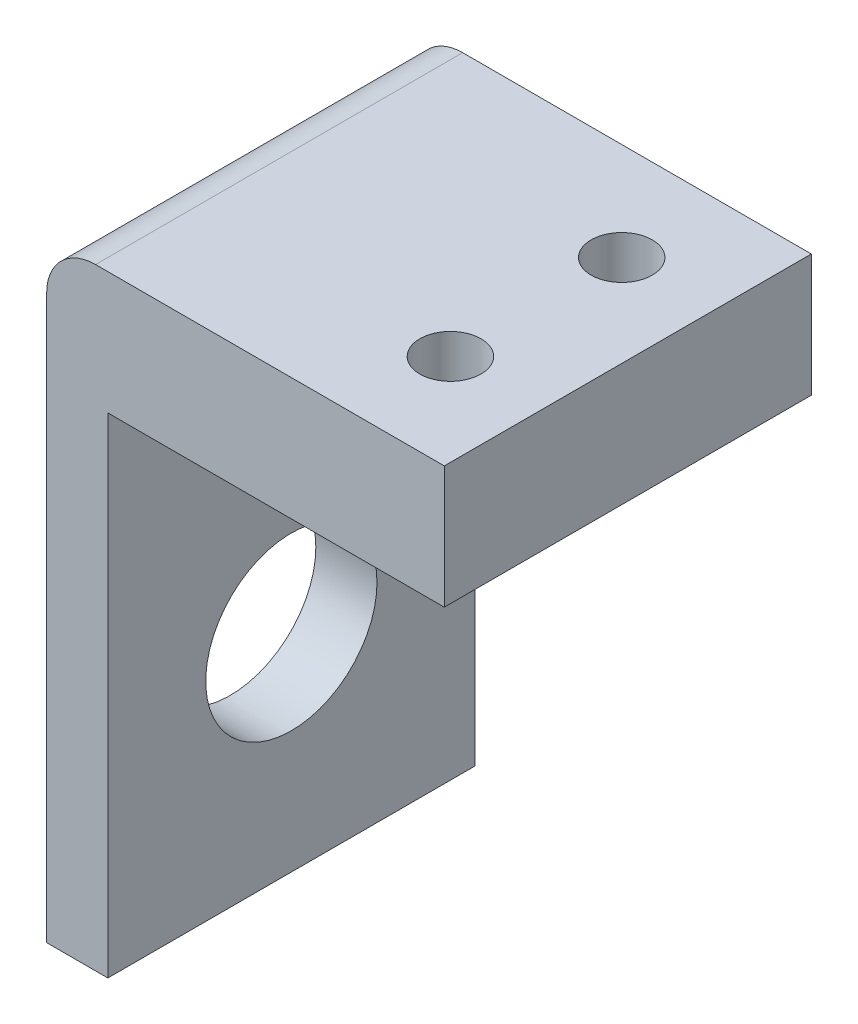
SolidWorks part; units mm, degrees
ref_plane "Front Plane" through (0, 0, 0) normal (0, 0, 1) x (1, 0, 0)
ref_plane "Top Plane" through (0, 0, 0) normal (0, 1, 0) x (1, 0, 0)
ref_plane "Right Plane" through (0, 0, 0) normal (1, 0, 0) x (0, 0, -1)
sketch "Sketch1" plane through (0, 0, 0) normal (1, 0, 0) x (0, 0, -1)
  line L0 (0, -7) -> (0, -17)
  line L1 (0, -17) -> (15, -17)
  line L2 (15, -17) -> (15, 33)
  line L3 (15, 33) -> (0, 33)
  line L4 (0, 33) -> (0, 23)
  line L5 (0, 23) -> (0, 7)
  line L6 (0, 33) -> (-15, 33)
  line L7 (-15, 33) -> (-15, -17)
  line L8 (-15, -17) -> (0, -17)
  line L9 (0, 23) -> (-15, 23)
  line L10 (0, 23) -> (15, 23)
  circle A0 centre (0, 0) radius 7
  dimension "D1" = 14
  dimension "D2" = 10
  dimension "D3" = 15
  dimension "D4" = 15
  dimension "D5" = 50
  dimension "D6" = 10
extrude "Boss-Extrude2" add sketch "Sketch1" along normal mid plane 5 contours A0 L5 L9 L7 L8 L0 | A0 L0 L1 L2 L10 L5 region at (0, 3.4415, -8.1665) region at (0, 3.4415, 8.1665)
extrude "Boss-Extrude3" add sketch "Sketch1<7>" along normal blind 30 and the other way blind 2.5 contours L9 L4 L6 L7 | L4 L10 L2 L3 region at (0, 28, 7.5) region at (0, 28, -7.5)
sketch "Sketch1<7>" plane through (0, 0, 0) normal (1, 0, 0) x (0, 0, -1) same geometry as "Sketch1"
sketch "Sketch2" plane through (0, 33, 0) normal (0, 1, 0) x (1, 0, 0)
  line L0 (30, 15) -> (30, -15)
  line L1 (30, -15) -> (15, -15)
  line L2 (-2.5, -15) -> (30, -15) construction
  line L3 (22.5, -15) -> (22.5, -7)
  line L4 (22.5, 15) -> (22.5, 7)
  line L5 (-2.5, 15) -> (30, 15) construction
  circle A0 centre (22.5, -7) radius 2.5
  circle A1 centre (22.5, 7) radius 2.5
  dimension "D3" = 5
  dimension "D4" = 5
  dimension "D1" = 8
  dimension "D2" = 8
extrude "Cut-Extrude1" cut sketch "Sketch2" against normal blind 13 contours A0 | A1 region at (24.2178, 33, 8.7178) region at (20.7822, 33, -5.2822)
fillet "Fillet1" radius 4 1 edges at (-2.5, 33, 0)
